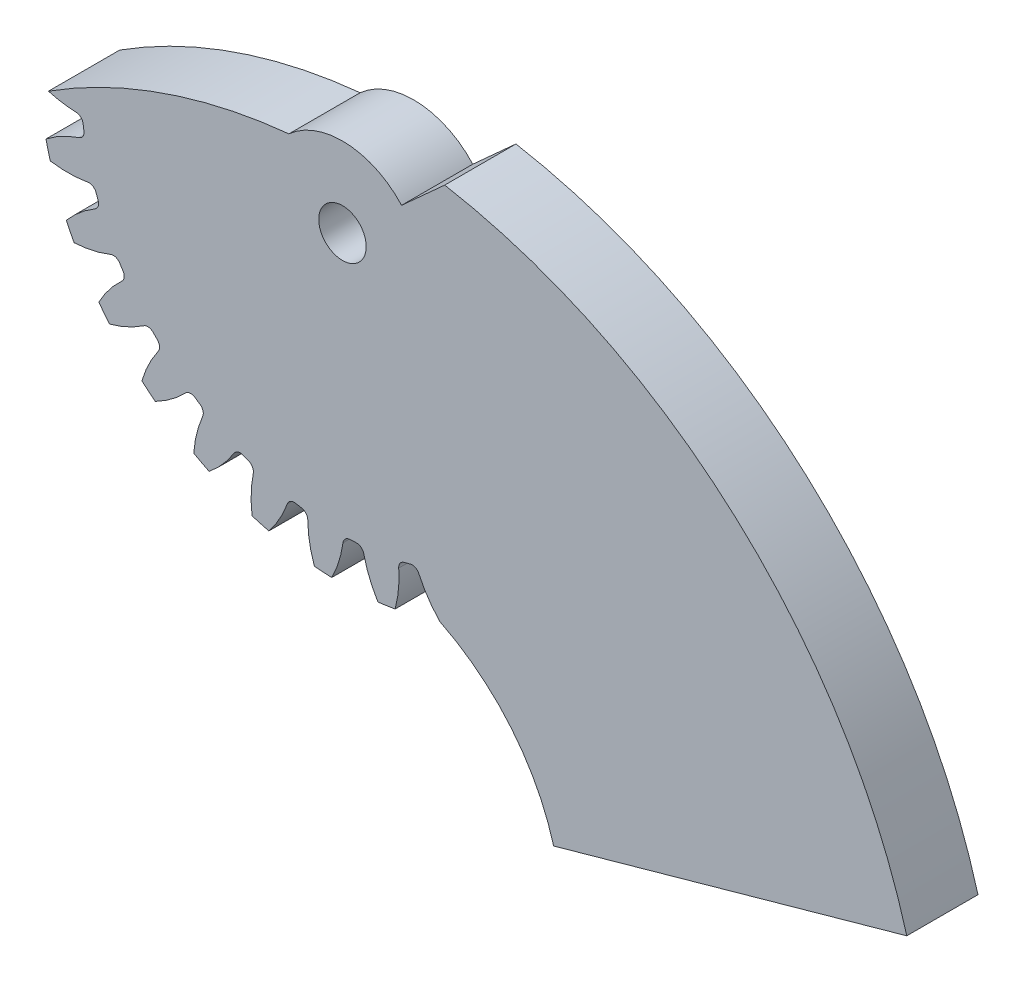
SolidWorks part; units mm, degrees
ref_plane "Front" through (0, 0, 0) normal (0, 0, 1) x (1, 0, 0)
ref_plane "Top" through (0, 0, 0) normal (0, 1, 0) x (1, 0, 0)
ref_plane "Right" through (0, 0, 0) normal (1, 0, 0) x (0, 0, -1)
sketch "Sketch3" plane through (0, 0, 0) normal (0, 0, 1) x (1, 0, 0)
  circle A0 centre (0, 0) radius 40.64
  dimension "od" = 81.28
extrude "gearBody" add sketch "Sketch3" along normal blind 9.525
sketch "Sketch2" plane through (0, 0, 0) normal (0, 0, 1) x (1, 0, 0)
  line L0 (0, 0) -> (34.0786, 14.1158) construction
  line L1 (45.4751, -11.4855) -> (0, 0) construction
  line L2 (0, 0) -> (36.3143, 0) construction
  line L3 (38.0972, -0.458) -> (37.8451, -4.4001) construction
  line L5 (37.9712, -2.4291) -> (0, 0) construction
  line L7 (0, 0) -> (36.8864, 0) construction
  arc A0 (36.879, -0.7403) -> (36.6727, -3.9649) centre (0, 0) ccw construction
  arc A1 (40.637, 0.4947) -> (40.2427, -5.6687) centre (0, 0) ccw construction
  arc A2 (38.0972, -0.458) -> (37.8451, -4.4001) centre (0, 0) ccw construction
  arc A3 (34.9015, -2.6404) -> (34.9534, -1.8283) centre (0, 0) ccw
  arc A4 (45.4751, -11.4855) -> (35.6466, -3.6712) centre (32.0022, -18.3431) ccw
  arc A5 (45.4751, -11.4855) -> (46.5679, 5.5974) centre (0, 0) ccw
  arc A6 (46.5679, 5.5974) -> (35.8238, -0.9008) centre (34.0786, 14.1158) cw
  arc A7 (34.9534, -1.8283) -> (35.8238, -0.9008) centre (35.9376, -1.8798) cw
  arc A8 (35.6466, -3.6712) -> (34.9015, -2.6404) centre (35.8842, -2.7147) cw
  point P6 (46.5679, 5.5974)
  point P22 (45.4751, -11.4855)
  dimension "baseDia" = 73.7729
  dimension "od" = 81.28
  dimension "pd" = 76.2
  dimension "rd" = 70.0024
  dimension "rFillet" = 0.9855
  dimension "pointX" = 46.5679
  dimension "pointY" = 5.5974
  dimension "CTT" = 3.9421
  dimension "flankCenterAngle" = 22.5
extrude "toothCut" cut sketch "Sketch2" along normal through all
pattern_circular "CirPattern1" count 30 over 360 about axis through (0, 0, 9.525) along (0, 0, -1) of "toothCut"
sketch "boreDia" plane through (0, 0, 0) normal (0, 0, 1) x (1, 0, 0)
  circle A0 centre (0, 0) radius 3.175
  dimension "boreDia" = 6.35
extrude "bore" cut sketch "boreDia" against normal mid plane 25400
sketch "Sketch4" plane through (0, 0, 9.525) normal (0, 0, 1) x (1, 0, 0)
  circle A1 centre (0, -64.77) radius 78.359
  arc A2 (-41.3654, 1.781) -> (41.3654, 1.781) centre (0, 0) cw
  dimension "D2" = 156.718
  dimension "D1" = 64.77
extrude "Cut-Extrude1" cut sketch "Sketch4" against normal through all contours A1 region at (0, 22.7553, 9.525)
sketch "Sketch6" plane through (0, 0, 9.525) normal (0, 0, 1) x (1, 0, 0)
  line L0 (0, -64.77) -> (-56.0105, -9.9708) construction
  line L1 (0, -64.77) -> (75.4628, -43.6631) construction
  line L2 (0, -64.77) -> (-7.1593, 7.9032) construction
  line L3 (-52.1978, -13.701) -> (-56.0105, -9.9708)
  line L4 (-7.1593, 7.9032) -> (-7.6823, 13.2115)
  circle A1 centre (0, -64.77) radius 78.359 construction
  arc A3 (-7.6823, 13.2115) -> (-56.0105, -9.9708) centre (0, -64.77) ccw
  arc A5 (-7.1593, 7.9032) -> (-52.1978, -13.701) centre (0, -64.77) ccw
  dimension "D2" = 73.025
  dimension "D3" = 156.718
  dimension "D6" = 78.359
  dimension "D1" = 120
  dimension "D4" = 40
  dimension "D5" = 6.35
extrude "Cut-Extrude2" cut sketch "Sketch6" against normal through all
sketch "Sketch8" plane through (0, 0, 9.525) normal (0, 0, 1) x (1, 0, 0)
  line L2 (0, -64.77) -> (79.1078, -42.6436) construction
  line L3 (0, -64.77) -> (-7.6823, 13.2115) construction
  line L4 (28.2434, -56.8703) -> (75.4628, -43.6631)
  line L5 (13.9737, 12.333) -> (13.028, -38.4952)
  arc A2 (13.9737, 12.333) -> (75.4628, -43.6631) centre (0, -64.77) cw
  arc A3 (34.5606, 5.5556) -> (-7.6823, 13.2115) centre (0, -64.77) ccw construction
  circle A4 centre (0, -64.77) radius 29.21 construction
  arc A5 (13.028, -38.4952) -> (28.2434, -56.8703) centre (0, -64.77) cw
  dimension "D1" = 58.42
  dimension "D2" = 80
extrude "Boss-Extrude3" add sketch "Sketch8" against normal through all
sketch "Sketch9" plane through (0, 0, 9.525) normal (0, 0, 1) x (1, 0, 0)
  line L1 (-7.1593, 7.9032) -> (-7.6823, 13.2115)
  line L2 (0, 0) -> (7.9032, 7.1593) construction
  line L3 (7.9032, 7.1593) -> (13.6738, 12.3867)
  arc A0 (-7.1593, 7.9032) -> (7.9032, 7.1593) centre (0, 0) cw
  arc A1 (75.4628, -43.6631) -> (-7.6823, 13.2115) centre (0, -64.77) ccw construction
  arc A3 (13.6738, 12.3867) -> (-7.6823, 13.2115) centre (0, -64.77) ccw
  dimension "D1" = 90
extrude "Cut-Extrude3" cut sketch "Sketch9" against normal through all
